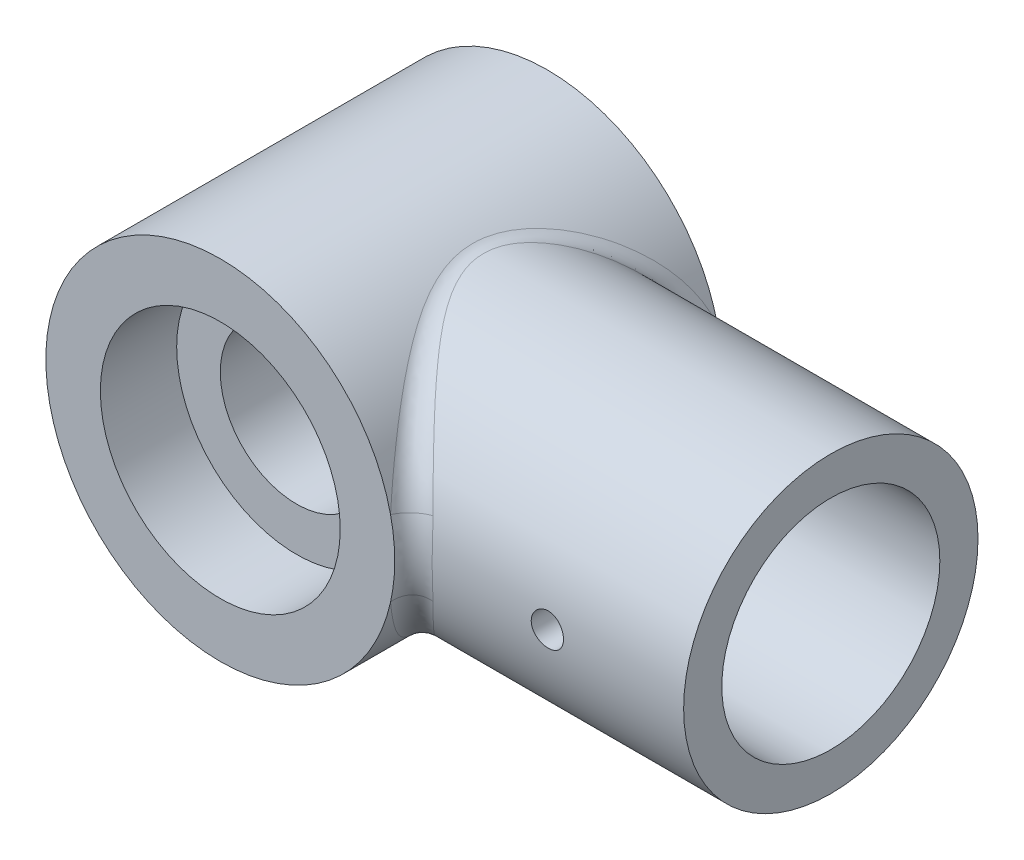
SolidWorks part; units mm, degrees
ref_plane "Front Plane" through (0, 0, 0) normal (0, 0, 1) x (1, 0, 0)
ref_plane "Top Plane" through (0, 0, 0) normal (0, 1, 0) x (1, 0, 0)
ref_plane "Right Plane" through (0, 0, 0) normal (1, 0, 0) x (0, 0, -1)
ref_plane "Plane1" through (0, 0, 0) normal (0, -1, 0) x (1, 0, 0)
sketch "Sketch1" plane through (0, 0, 0) normal (0, -1, 0) x (1, 0, 0)
  line L0 (16, 30) -> (0, 30)
  line L1 (0, 30) -> (0, 0)
  line L2 (0, 0) -> (16, 0)
  line L3 (16, 0) -> (16, 30)
  line L4 (0, 30) -> (0, 0) construction
revolve "Revolve1" add sketch "Sketch1" angle 360 about L4 reverse direction yes
ref_plane "Plane2" through (0, -4.2549, 1.3238) normal (0, 0.9549, -0.2971) x (-1, 0, 0)
sketch "Sketch2" plane through (0, -4.2549, 1.3238) normal (0, 0.9549, -0.2971) x (-1, 0, 0)
  line L0 (-8.5878, 14.3228) -> (-8.5878, 27.8228)
  line L1 (-8.5878, 27.8228) -> (-41, 27.8228)
  line L2 (-41, 27.8228) -> (-41, 14.3228)
  line L3 (-41, 14.3228) -> (-8.5878, 14.3228)
  line L4 (-41, 14.3228) -> (-8.5878, 14.3228) construction
revolve "Revolve2" add sketch "Sketch2" angle 360 about L4 reverse direction yes
sketch "Sketch3" plane through (0, 0, 0) normal (0, -1, 0) x (1, 0, 0)
  line L0 (11, 30) -> (0, 30)
  line L1 (0, 30) -> (0, 0)
  line L2 (0, 0) -> (11, 0)
  line L3 (11, 0) -> (11, 7)
  line L4 (11, 7) -> (7, 7)
  line L5 (7, 7) -> (7, 23)
  line L6 (7, 23) -> (11, 23)
  line L7 (11, 23) -> (11, 30)
  line L8 (0, 30) -> (0, 0) construction
revolve "Cut-Revolve1" cut sketch "Sketch3" angle 360 about L8 reverse direction yes
hole_wizard "Ø20.0 (20) Diameter Hole1" positions "Sketch5" profile "Sketch4" hole size "Ø20.0" standard "ANSI Metric"
sketch "Sketch5" plane through (41, 0, 0) normal (1, 0, 0) x (0, 0, -1)
  point P0 (-15, 0)
sketch "Sketch4" plane through (41, 0, 15) normal (0, 1, 0) x (0, 0, -1)
  line L0 (0, 0) -> (0, 25)
  line L1 (0, 25) -> (10, 25)
  line L2 (10, 25) -> (10, 0)
  line L5 (10, 0) -> (0, 0)
  line L10 (0, 25) -> (-10, 25) construction
  line L11 (0, -6.35) -> (0, 107.95) construction
  dimension "Hole Dia." = 20
  dimension "Hole Depth" = 25
  dimension "Drill Angle" = 180
ref_plane "Plane3" through (0, 0, 5.202) normal (0, 0, 1) x (1, 0, 0)
hole_wizard "Ø4.0 (2.96) Diameter Hole1" positions "Sketch7" profile "Sketch6" hole size "Ø4.0" standard "ANSI Metric" end condition through all
sketch "Sketch7" plane through (0, 0, 5.202) normal (0, 0, 1) x (1, 0, 0)
  point P0 (28.5, 0)
sketch "Sketch6" plane through (28.5, 0, 5.202) normal (1, 0, 0) x (0, -1, 0)
  line L0 (0, 0) -> (0, 5.202)
  line L1 (0, 5.202) -> (1.48, 5.202)
  line L2 (1.48, 5.202) -> (1.48, 0)
  line L5 (1.48, 0) -> (0, 0)
  line L11 (0, -6.35) -> (0, 107.95) construction
  dimension "Thru Hole Dia." = 2.96
  dimension "Thru Hole Depth" = 5.202
fillet "Fillet1" radius 2.0001 1 edges at (15.568, 3.6927, 2.0149) tangent propagation no
ref_plane "Plane4" through (0, 0, 15) normal (0, 0, -1) x (-1, 0, 0)
sketch "Sketch8" plane through (0, 0, 15) normal (0, 0, -1) x (-1, 0, 0)
  circle A0 centre (-28.5, 0) radius 1.48
  circle A1 centre (-28.5, 0) radius 1.48 construction
extrude "Cut-Extrude1" cut sketch "Sketch8" against normal through all
scale "Scale1" scale about origin uniform scaling yes scale factor 1.25
